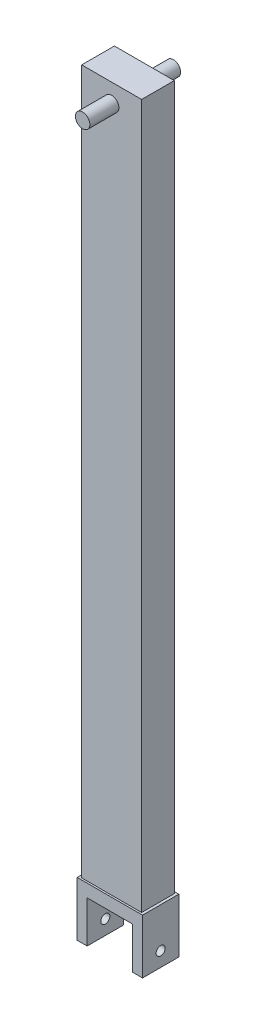
SolidWorks part; units mm, degrees
ref_plane "Front Plane" through (0, 0, 0) normal (0, 0, 1) x (1, 0, 0)
ref_plane "Top Plane" through (0, 0, 0) normal (0, 1, 0) x (1, 0, 0)
ref_plane "Right Plane" through (0, 0, 0) normal (1, 0, 0) x (0, 0, -1)
sketch "Sketch1" plane through (0, 0, 0) normal (0, 1, 0) x (1, 0, 0)
  line L1 (-16.5, 9) -> (16.5, 9)
  line L2 (-16.5, 9) -> (-16.5, -9)
  line L3 (-16.5, -9) -> (16.5, -9)
  line L4 (16.5, 9) -> (16.5, -9)
  line L5 (-16.5, 9) -> (16.5, -9) construction
  line L6 (-16.5, -9) -> (16.5, 9) construction
  point P0 (0, 0)
extrude "Boss-Extrude1" add sketch "Sketch1" along normal blind 388
ref_plane "Plane1" through (0, 0, 0) normal (0, 0, 1) x (1, 0, 0)
sketch "Sketch3" plane through (0, 0, 0) normal (0, 0, 1) x (1, 0, 0)
  line L0 (-16.5, 388) -> (16.5, 388) construction
  circle A0 centre (0, 377.75) radius 4
  dimension "D1" = 10.25
extrude "Boss-Extrude2" add sketch "Sketch3" along normal mid plane 50
sketch "Sketch4" plane through (0, 0, 0) normal (0, -1, 0) x (1, 0, 0)
  line L1 (-18, 10) -> (18, 10)
  line L2 (-18, 10) -> (-18, -10)
  line L3 (-18, -10) -> (18, -10)
  line L4 (18, 10) -> (18, -10)
  line L5 (-18, 10) -> (18, -10) construction
  line L6 (-18, -10) -> (18, 10) construction
  point P0 (0, 0)
extrude "Boss-Extrude3" add sketch "Sketch4" along normal blind 30
sketch "Sketch5" plane through (0, 0, 10) normal (0, 0, 1) x (1, 0, 0)
  line L0 (18, -30) -> (-18, -30) construction
  line L1 (-12.5, -52.9912) -> (12.5, -52.9912)
  line L2 (-12.5, -52.9912) -> (-12.5, -7.0088)
  line L3 (-12.5, -7.0088) -> (12.5, -7.0088)
  line L4 (12.5, -52.9912) -> (12.5, -7.0088)
  line L5 (-12.5, -52.9912) -> (12.5, -7.0088) construction
  line L6 (-12.5, -7.0088) -> (12.5, -52.9912) construction
  point P0 (0, -30)
extrude "Cut-Extrude1" cut sketch "Sketch5" against normal through all
sketch "Sketch6" plane through (18, 0, 0) normal (1, 0, 0) x (0, 0, -1)
  line L0 (0, 18.15) -> (0, -18.15) construction
  line L1 (10, -30) -> (-10, -30) construction
  circle A0 centre (0, -22) radius 2.5
  dimension "D1" = 8
extrude "Cut-Extrude2" cut sketch "Sketch6" against normal through all
